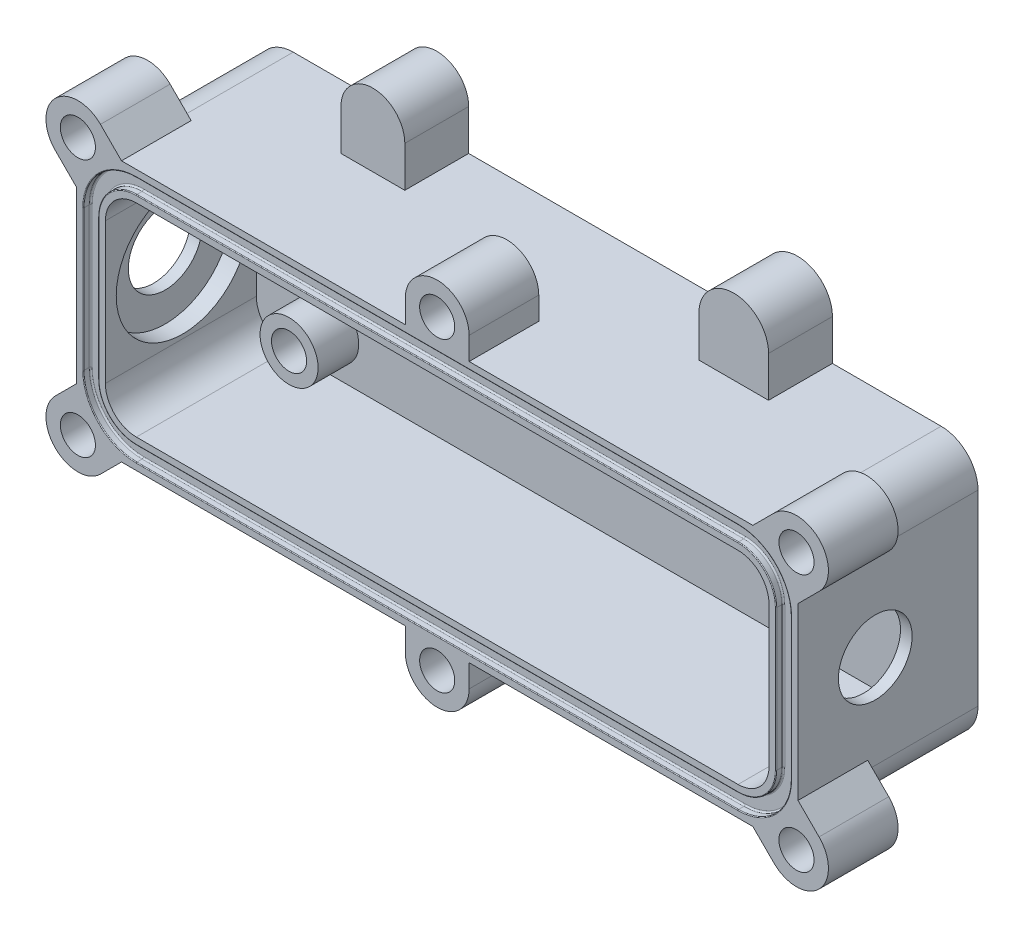
SolidWorks part; units mm, degrees
material "ABS"
ref_plane "X-Y Datum" through (0, 0, 0) normal (0, 0, 1) x (1, 0, 0)
ref_plane "X-Z Datum" through (0, 0, 0) normal (0, 1, 0) x (1, 0, 0)
ref_plane "Y-Z Datum" through (0, 0, 0) normal (1, 0, 0) x (0, 0, -1)
sketch "Sketch1" plane through (0, 0, 0) normal (0, 0, 1) x (1, 0, 0)
  line L1 (-48.9585, 14.1605) -> (48.9585, 14.1605) construction
  line L2 (-48.9585, 14.1605) -> (-48.9585, -14.1605) construction
  line L3 (-48.9585, -14.1605) -> (48.9585, -14.1605) construction
  line L4 (48.9585, 14.1605) -> (48.9585, -14.1605) construction
  line L5 (-48.9585, 14.1605) -> (48.9585, -14.1605) construction
  line L6 (-48.9585, -14.1605) -> (48.9585, 14.1605) construction
  line L7 (-57.15, 17.4625) -> (57.15, 17.4625)
  line L8 (-57.15, 17.4625) -> (-57.15, -17.4625)
  line L9 (-57.15, -17.4625) -> (57.15, -17.4625)
  line L10 (57.15, 17.4625) -> (57.15, -17.4625)
  line L11 (-57.15, 17.4625) -> (57.15, -17.4625) construction
  line L12 (-57.15, -17.4625) -> (57.15, 17.4625) construction
  point P0 (0, 0)
  point P6 (0, 0)
  dimension "D1" = 97.917
  dimension "D2" = 28.321
  dimension "D3" = 114.3
  dimension "D4" = 34.925
extrude "Boss-Extrude1" add sketch "Sketch1" along normal blind 26
shell "Shell1" thickness 5 removed face at (0, 0, 26) outward yes
fillet "Fillet1" radius 5.334 4 edges at (-57.15, 17.4625, 13) (-57.15, -17.4625, 13) (57.15, -17.4625, 13) (57.15, 17.4625, 13)
fillet "Fillet2" radius 6.35 4 edges at (62.15, -22.4625, 10.5) (62.15, 22.4625, 10.5) (-62.15, 22.4625, 10.5) (-62.15, -22.4625, 10.5)
sketch "Sketch2" plane through (0, 0, 26) normal (0, 0, 1) x (1, 0, 0)
  line L20 (-60.9327, 12.1285) -> (-60.9327, -12.1285)
  line L21 (-51.816, -21.2452) -> (51.816, -21.2452)
  line L22 (60.9327, -12.1285) -> (60.9327, 12.1285)
  line L23 (51.816, 21.2452) -> (-51.816, 21.2452)
  line L24 (59.65, -12.1285) -> (59.65, 12.1285)
  line L25 (-51.816, -19.9625) -> (51.816, -19.9625)
  line L26 (-59.65, 12.1285) -> (-59.65, -12.1285)
  line L27 (51.816, 19.9625) -> (-51.816, 19.9625)
  line L28 (59.65, -12.1285) -> (59.65, 12.1285) construction
  line L29 (-51.816, -19.9625) -> (51.816, -19.9625) construction
  line L30 (-59.65, 12.1285) -> (-59.65, -12.1285) construction
  line L31 (51.816, 19.9625) -> (-51.816, 19.9625) construction
  line L32 (51.816, 18.6798) -> (-51.816, 18.6798)
  line L33 (-58.3673, 12.1285) -> (-58.3673, -12.1285)
  line L34 (-51.816, -18.6798) -> (51.816, -18.6798)
  line L35 (58.3673, -12.1285) -> (58.3673, 12.1285)
  arc A16 (-51.816, 21.2452) -> (-60.9327, 12.1285) centre (-51.816, 12.1285) ccw
  arc A17 (-60.9327, -12.1285) -> (-51.816, -21.2452) centre (-51.816, -12.1285) ccw
  arc A18 (51.816, -21.2452) -> (60.9327, -12.1285) centre (51.816, -12.1285) ccw
  arc A19 (60.9327, 12.1285) -> (51.816, 21.2452) centre (51.816, 12.1285) ccw
  arc A20 (59.65, 12.1285) -> (51.816, 19.9625) centre (51.816, 12.1285) ccw
  arc A21 (51.816, -19.9625) -> (59.65, -12.1285) centre (51.816, -12.1285) ccw
  arc A22 (-59.65, -12.1285) -> (-51.816, -19.9625) centre (-51.816, -12.1285) ccw
  arc A23 (-51.816, 19.9625) -> (-59.65, 12.1285) centre (-51.816, 12.1285) ccw
  arc A24 (59.65, 12.1285) -> (51.816, 19.9625) centre (51.816, 12.1285) ccw construction
  arc A25 (51.816, -19.9625) -> (59.65, -12.1285) centre (51.816, -12.1285) ccw construction
  arc A26 (-59.65, -12.1285) -> (-51.816, -19.9625) centre (-51.816, -12.1285) ccw construction
  arc A27 (-51.816, 19.9625) -> (-59.65, 12.1285) centre (-51.816, 12.1285) ccw construction
  arc A28 (-51.816, 18.6798) -> (-58.3673, 12.1285) centre (-51.816, 12.1285) ccw
  arc A29 (-58.3673, -12.1285) -> (-51.816, -18.6798) centre (-51.816, -12.1285) ccw
  arc A30 (51.816, -18.6798) -> (58.3673, -12.1285) centre (51.816, -12.1285) ccw
  arc A31 (58.3673, 12.1285) -> (51.816, 18.6798) centre (51.816, 12.1285) ccw
  dimension "D1" = 2.5
  dimension "D2" = 1.2827
  dimension "D3" = 1.2827
extrude "Cut-Extrude1" cut sketch "Sketch2" against normal blind 1.2446
fillet "Fillet3" radius 0.254 16 edges at (-58.3673, 0, 24.7554) (-56.4485, 16.761, 24.7554) (0, 18.6798, 24.7554) (56.4485, 16.761, 24.7554) (58.3673, 0, 24.7554) (56.4485, -16.761, 24.7554) (0, -18.6798, 24.7554) (-58.2625, 18.575, 24.7554) (0, 21.2452, 24.7554) (58.2625, 18.575, 24.7554) (60.9327, 0, 24.7554) (58.2625, -18.575, 24.7554) (0, -21.2452, 24.7554) (-58.2625, -18.575, 24.7554) (-56.4485, -16.761, 24.7554) (-60.9327, 0, 24.7554)
fillet "Fillet4" radius 0.127 16 edges at (-58.3673, 0, 26) (-56.4485, 16.761, 26) (0, 18.6798, 26) (56.4485, 16.761, 26) (58.3673, 0, 26) (56.4485, -16.761, 26) (0, -18.6798, 26) (-58.2625, 18.575, 26) (0, 21.2452, 26) (58.2625, 18.575, 26) (60.9327, 0, 26) (58.2625, -18.575, 26) (0, -21.2452, 26) (-58.2625, -18.575, 26) (-56.4485, -16.761, 26) (-60.9327, 0, 26)
sketch "Sketch4" plane through (0, 0, 26) normal (0, 0, 1) x (1, 0, 0)
  line L0 (51.816, -12.1285) -> (61.8878, -22.2003) construction
  line L1 (54.3718, -22.4625) -> (57.9987, -26.0894)
  line L2 (62.15, -16.1125) -> (62.15, 16.1125) construction
  line L3 (-55.8, -22.4625) -> (55.8, -22.4625) construction
  line L4 (62.15, -14.6843) -> (65.7769, -18.3112)
  circle A2 centre (61.8878, -22.2003) radius 3.025
  circle A4 centre (61.8878, -22.2003) radius 5.5
  arc A5 (51.816, -21.3722) -> (61.0597, -12.1285) centre (51.816, -12.1285) ccw construction
  arc A6 (51.816, -21.3722) -> (61.0597, -12.1285) centre (51.816, -12.1285) ccw
  point P8 (58.3523, -18.6648)
  dimension "D1" = 6.05
  dimension "D2" = 11
  dimension "D3" = 5
extrude "Boss-Extrude3" add sketch "Sketch4" against normal blind 12
sketch "Sketch5" plane through (0, 0, 26) normal (0, 0, 1) x (1, 0, 0)
  circle A2 centre (61.8878, -22.2003) radius 3.025 construction
  circle A3 centre (61.8878, -22.2003) radius 3.025
  dimension "D1" = 6.05
extrude "Cut-Extrude3" cut sketch "Sketch5" against normal blind 9
mirror "Mirror1" about plane through (0, 0, 0) normal (0, 1, 0) of "Cut-Extrude3", "Boss-Extrude3"
mirror "Mirror2" about plane through (0, 0, 0) normal (1, 0, 0) of "Mirror1", "Cut-Extrude3", "Boss-Extrude3"
sketch "Sketch6" plane through (0, 0, 26) normal (0, 0, 1) x (1, 0, 0)
  line L0 (0, -22.4625) -> (0, -26.3722)
  line L1 (-54.3718, -22.4625) -> (54.3718, -22.4625) construction
  line L2 (51.816, -21.3722) -> (-51.816, -21.3722) construction
  line L3 (51.816, -21.3722) -> (-51.816, -21.3722)
  line L4 (-5.5, -26.3722) -> (-5.5, -22.4625)
  line L5 (5.5, -26.3722) -> (5.5, -22.4625)
  circle A0 centre (0, -26.3722) radius 5.5
  circle A1 centre (0, -26.3722) radius 3.025
  dimension "D2" = 11
  dimension "D3" = 6.05
  dimension "D1" = 5
extrude "Boss-Extrude4" add sketch "Sketch6" against normal blind 12
sketch "Sketch7" plane through (0, 0, 26) normal (0, 0, 1) x (1, 0, 0)
  circle A0 centre (0, -26.3722) radius 3.025 construction
  circle A1 centre (0, -26.3722) radius 3.025
  dimension "D1" = 6.05
extrude "Cut-Extrude4" cut sketch "Sketch7" against normal blind 9
mirror "Mirror3" about plane through (0, 0, 0) normal (0, 1, 0) of "Cut-Extrude4", "Boss-Extrude4"
sketch "Sketch9" plane through (62.15, 0, 0) normal (1, 0, 0) x (0, 0, -1)
  line L0 (-26, 0) -> (5, 0) construction
  line L1 (-26, -14.6843) -> (-26, 14.6843) construction
  line L2 (5, -16.1125) -> (5, 16.1125) construction
  line L3 (0, -12.1285) -> (0, 12.1285) construction
  circle A0 centre (-12.7, 0) radius 6.35
  circle A1 centre (-12.7, 0) radius 11.43
  dimension "D1" = 12.7
  dimension "D3" = 22.86
  dimension "D2" = 12.7
extrude "Cut-Extrude5" cut sketch "Sketch9" against normal blind 6 contours L0 A0 | A0 L0
sketch "Sketch10" plane through (0, 0, 0) normal (0, 0, 1) x (1, 0, 0)
  circle A0 centre (-44.5135, 10.4775) radius 3.025
  circle A1 centre (-44.5135, -10.4775) radius 3.025
  circle A2 centre (44.1265, -0.0975) radius 3.025
  circle A3 centre (-44.5135, 10.4775) radius 5
  circle A4 centre (-44.5135, -10.4775) radius 5
  circle A5 centre (44.1265, -0.0975) radius 5
  point P0 (-44.5135, 10.4775)
  point P1 (-44.5135, -10.4775)
  point P3 (44.1265, -0.0975)
  dimension "D1" = 6.05
  dimension "D2" = 10
extrude "Boss-Extrude5" add sketch "Sketch10" along normal blind 7
sketch "Sketch11" plane through (57.15, 0, 0) normal (-1, 0, 0) x (0, 0, 1)
  circle A0 centre (12.7, 0) radius 11.43 construction
  circle A1 centre (12.7, 0) radius 11.43
  dimension "D1" = 22.86
extrude "Cut-Extrude6" cut sketch "Sketch11" against normal blind 3
mirror "Mirror4" about plane through (0, 0, 0) normal (1, 0, 0) of "Cut-Extrude6", "Cut-Extrude5"
sketch "Sketch12" plane through (0, 0, -5) normal (0, 0, -1) x (-1, 0, 0)
  line L0 (-62.15, 22.4625) -> (0, 22.4625)
  line L1 (-62.15, 22.4625) -> (62.15, 22.4625)
  line L2 (-62.15, 22.4625) -> (-62.15, -22.4625) construction
  line L3 (-62.15, -22.4625) -> (62.15, -22.4625) construction
  line L4 (62.15, 22.4625) -> (62.15, -22.4625) construction
  line L5 (-62.15, 22.4625) -> (62.15, -22.4625) construction
  line L6 (-62.15, -22.4625) -> (62.15, 22.4625) construction
  line L7 (0, 22.4625) -> (-31.075, 22.4625)
  line L8 (-31.075, 22.4625) -> (-31.075, 29.4625) construction
  line L9 (0, 22.4625) -> (62.15, 22.4625)
  line L10 (31.075, 22.4625) -> (31.075, 29.4625) construction
  line L11 (-37.075, 29.4625) -> (-37.075, 22.4625)
  line L12 (-25.075, 29.4625) -> (-25.075, 22.4625)
  line L13 (25.575, 29.4625) -> (25.575, 22.4625)
  line L14 (36.575, 29.4625) -> (36.575, 22.4625)
  circle A0 centre (-31.075, 29.4625) radius 3.025
  circle A1 centre (31.075, 29.4625) radius 3.025
  circle A2 centre (-31.075, 29.4625) radius 6
  circle A3 centre (31.075, 29.4625) radius 5.5
  dimension "D1" = 6.05
  dimension "D2" = 12
  dimension "D3" = 11
  dimension "D4" = 7
extrude "Boss-Extrude6" add sketch "Sketch12" against normal blind 11 contours A2 L11 L1 L7 L12 | A2 A0 | A0 | A3 L13 L9 L14 | A3 A1 | A1
sketch "Sketch13" plane through (0, 0, -5) normal (0, 0, -1) x (-1, 0, 0)
  circle A1 centre (31.075, 29.4625) radius 5.5
  circle A2 centre (31.075, 29.4625) radius 5.5
  circle A3 centre (-31.075, 29.4625) radius 6
  circle A4 centre (-31.075, 29.4625) radius 6
  circle A5 centre (31.075, 29.4625) radius 3.025
  circle A6 centre (31.075, 29.4625) radius 3.025
  circle A7 centre (-31.075, 29.4625) radius 3.025
  circle A8 centre (-31.075, 29.4625) radius 3.025
  dimension "D1" = 0
  dimension "D2" = 0
  dimension "D3" = 0
  dimension "D4" = 0
extrude "Cut-Extrude7" cut sketch "Sketch13" against normal blind 9 contours A8 | A6
